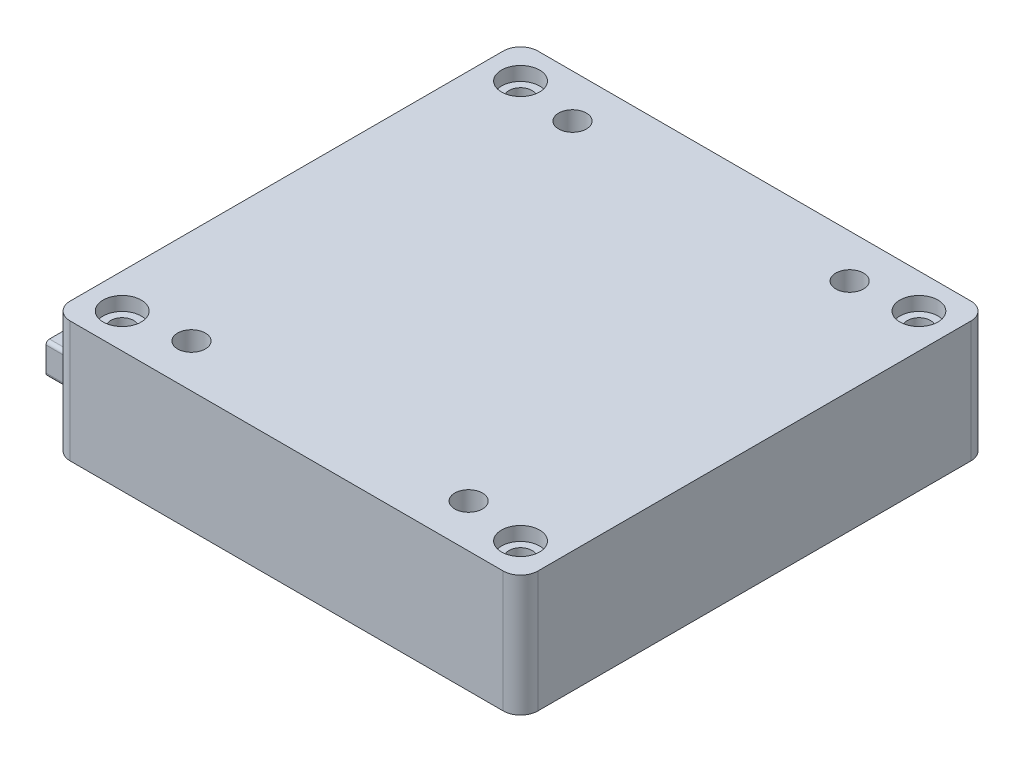
SolidWorks part; units mm, degrees
ref_plane "Front Plane" through (0, 0, 0) normal (0, 0, 1) x (1, 0, 0)
ref_plane "Top Plane" through (0, 0, 0) normal (0, 1, 0) x (1, 0, 0)
ref_plane "Right Plane" through (0, 0, 0) normal (1, 0, 0) x (0, 0, -1)
sketch "Sketch2" plane through (0, 0, 0) normal (0, 1, 0) x (1, 0, 0)
  line L1 (67.5, 67.5) -> (-67.5, 67.5)
  line L2 (67.5, 67.5) -> (67.5, -67.5)
  line L3 (67.5, -67.5) -> (-67.5, -67.5)
  line L4 (-67.5, 67.5) -> (-67.5, -67.5)
  line L5 (67.5, 67.5) -> (-67.5, -67.5) construction
  line L6 (67.5, -67.5) -> (-67.5, 67.5) construction
  point P0 (0, 0)
  dimension "D1" = 135
extrude "Boss-Extrude1" add sketch "Sketch2" along normal blind 35
fillet "Fillet1" radius 5 4 edges at (67.5, 17.5, -67.5) (67.5, 17.5, 67.5) (-67.5, 17.5, 67.5) (-67.5, 17.5, -67.5)
hole_wizard "CBORE for M6 Hex Head Bolt1" positions "3DSketch1" profile "Sketch6" counterbore size "M6" standard "DIN"
sketch3d "3DSketch1"
  line L0 (62.5, 35, -67.5) -> (-62.5, 35, -67.5) construction
  line L1 (-67.5, 35, -62.5) -> (-67.5, 35, 62.5) construction
  point P0 (-57.5, 35, -57.5)
  point P12 (0, 0, 0)
  dimension "D1" = 10
  dimension "D2" = 10
sketch "Sketch6" plane through (-57.5, 35, -57.5) normal (1, 0, 0) x (0, 0, 1)
  line L0 (0, 0) -> (0, 43.9828)
  line L1 (0, 43.9828) -> (3.3, 42)
  line L2 (3.3, 42) -> (3.3, 4)
  line L3 (3.3, 4) -> (5.5, 4)
  line L4 (5.5, 4) -> (5.5, 0)
  line L5 (5.5, 0) -> (0, 0)
  line L10 (0, 43.9828) -> (-3.3, 42) construction
  line L11 (0, -6.35) -> (0, 107.95) construction
  dimension "Hole Dia." = 6.6
  dimension "Hole Depth" = 42
  dimension "C'Bore Dia." = 11
  dimension "C'Bore Depth" = 4
  dimension "Drill Angle" = 118
ref_axis "Axis1" through (0, -1.75, 0) along (0, 1, 0)
sketch "Sketch7" plane through (-67.5, 0, 0) normal (-1, 0, 0) x (0, 0, 1)
  line L0 (0, -1.75) -> (0, 36.75) construction
  line L1 (60, 19) -> (-60, 19)
  line L2 (60, 19) -> (60, 5)
  line L3 (60, 5) -> (-60, 5)
  line L4 (-60, 19) -> (-60, 5)
  line L5 (60, 19) -> (-60, 5) construction
  line L6 (60, 5) -> (-60, 19) construction
  line L7 (-62.5, 0) -> (62.5, 0) construction
  point P0 (0, 12)
  dimension "D1" = 5
  dimension "D2" = 120
  dimension "D3" = 14
extrude "Boss-Extrude2" add sketch "Sketch7" along normal blind 2 separate body
fillet "Fillet2" radius 2 4 edges at (-68.5, 5, -60) (-68.5, 5, 60) (-68.5, 19, 60) (-68.5, 19, -60)
sketch "Sketch9" plane through (-69.5, 0, 0) normal (-1, 0, 0) x (0, 0, 1)
  line L0 (0, 19) -> (0, 5) construction
  line L1 (58, 19) -> (-58, 19) construction
  line L2 (-58, 5) -> (58, 5) construction
  line L3 (56.5, 15.5) -> (-56.5, 15.5)
  line L4 (56.5, 16.5) -> (-56.5, 16.5)
  line L5 (57.5, 15.5) -> (57.5, 8.5)
  line L6 (56.5, 7.5) -> (-56.5, 7.5)
  line L7 (-57.5, 15.5) -> (-57.5, 8.5)
  line L8 (57.5, 16.5) -> (-57.5, 7.5) construction
  line L9 (57.5, 7.5) -> (-57.5, 16.5) construction
  line L10 (-56.5, 15.5) -> (-56.5, 8.5)
  line L11 (56.5, 8.5) -> (-56.5, 8.5)
  line L12 (56.5, 15.5) -> (56.5, 8.5)
  arc A0 (56.5, 16.5) -> (57.5, 15.5) centre (56.5, 15.5) cw
  arc A1 (57.5, 8.5) -> (56.5, 7.5) centre (56.5, 8.5) cw
  arc A2 (-56.5, 7.5) -> (-57.5, 8.5) centre (-56.5, 8.5) cw
  arc A3 (-56.5, 16.5) -> (-57.5, 15.5) centre (-56.5, 15.5) ccw
  arc A4 (-56.5, 15.5) -> (-56.5, 15.5) centre (-56.5, 15.5) ccw
  arc A5 (-56.5, 8.5) -> (-56.5, 8.5) centre (-56.5, 8.5) cw
  arc A6 (56.5, 8.5) -> (56.5, 8.5) centre (56.5, 8.5) cw
  arc A7 (56.5, 15.5) -> (56.5, 15.5) centre (56.5, 15.5) cw
  point P6 (0, 12)
  dimension "D3" = 1
  dimension "D1" = 9
  dimension "D2" = 115
  dimension "D4" = 1
extrude "Boss-Extrude3" add sketch "Sketch9" along normal blind 10
sketch "Sketch12" plane through (0, 35, 0) normal (0, 1, 0) x (1, 0, 0)
  circle A0 centre (-40, 55) radius 4
  dimension "D1" = 8
  dimension "D2" = 55
  dimension "D3" = 40
extrude "Cut-Extrude1" cut sketch "Sketch12" against normal blind 10
mirror "Mirror3" about plane through (0, 0, 0) normal (0, 0, 1) of "CBORE for M6 Hex Head Bolt1", "Cut-Extrude1"
mirror "Mirror4" about plane through (0, 0, 0) normal (1, 0, 0) of "Mirror3"
